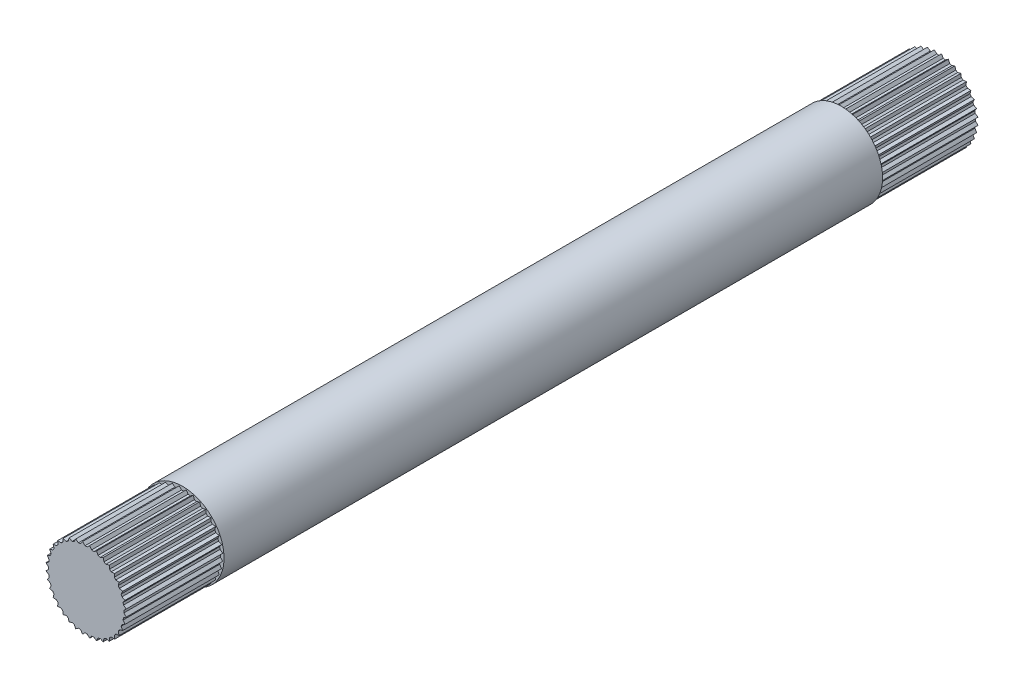
SolidWorks part; units mm, degrees
material "AISI 1015 Steel, Cold Drawn (SS)"
ref_plane "X-Y Datum" through (0, 0, 0) normal (0, 0, 1) x (1, 0, 0)
ref_plane "X-Z Datum" through (0, 0, 0) normal (0, 1, 0) x (1, 0, 0)
ref_plane "Y-Z Datum" through (0, 0, 0) normal (1, 0, 0) x (0, 0, -1)
sketch "Sketch9" plane through (0, 0, 0) normal (0, 1, 0) x (1, 0, 0)
  line L0 (16.002, 0) -> (0, 0)
  line L1 (0, 0) -> (0, -239.8166)
  line L2 (0, -239.8166) -> (-72.2493, -375.6979)
  dimension "D1" = 153.895
  dimension "D2" = 28
  dimension "D3" = 239.8166
  dimension "D5" = 16.002
sketch "Sketch5" plane through (0, 0, 0) normal (0, 1, 0) x (1, 0, 0)
  line L0 (7.9375, -218.2266) -> (7.9375, -22.1615)
  line L1 (7.9375, -22.1615) -> (9.525, -22.1615)
  line L2 (9.525, -22.1615) -> (9.525, -218.2266)
  line L3 (9.525, -218.2266) -> (7.9375, -218.2266)
  line L5 (16.002, 0) -> (0, 0) construction
  line L6 (0, 0) -> (0, -239.8166) construction
  line L7 (0, -239.8166) -> (9.525, -239.8166) construction
  line L8 (12.5602, -220.5666) -> (0, -220.5666) construction
  dimension "D1" = 1.5875
  dimension "D2" = 22.1615
  dimension "D3" = 7.9375
  dimension "D4" = 19.25
  dimension "D5" = 21.59
revolve "Revolve2" add sketch "Sketch5" angle 360 about L1
sketch "Sketch6" plane through (0, 0, 0) normal (0, 1, 0) x (1, 0, 0)
  circle A0 centre (0, -33.1635) radius 1.5875 construction
  circle A1 centre (0, -33.1635) radius 1.5875
sketch "Sketch7" plane through (0, 0, 0) normal (1, 0, 0) x (0, 0, -1)
  circle A2 centre (-39.196, 0) radius 1.5875
  circle A4 centre (-39.196, 0) radius 1.5875 construction
extrude "Cut-Extrude5" [suppressed] cut sketch "Sketch7" against normal through all both and the other way through all
extrude "Cut-Extrude6" [suppressed] cut sketch "Sketch6" against normal through all both and the other way through all
sketch "Sketch8" plane through (0, 0, 0) normal (0, 0, 1) x (1, 0, 0)
  line L0 (9.2357, -0.808) -> (8.6817, -0.254)
  line L1 (8.6817, -0.254) -> (8.6817, 0.254)
  line L2 (8.6817, 0.254) -> (9.2357, 0.808)
  line L3 (8.6817, 0) -> (0, 0) construction
  line L4 (8.9551, -2.3995) -> (8.5057, -1.7577)
  line L5 (8.5057, -1.7577) -> (8.5939, -1.2574)
  line L6 (8.5939, -1.2574) -> (9.2357, -0.808)
  line L7 (8.4024, -3.9181) -> (8.0713, -3.208)
  line L8 (8.0713, -3.208) -> (8.245, -2.7306)
  line L9 (8.245, -2.7306) -> (8.9551, -2.3995)
  line L10 (7.5944, -5.3176) -> (7.3916, -4.5608)
  line L11 (7.3916, -4.5608) -> (7.6456, -4.1209)
  line L12 (7.6456, -4.1209) -> (8.4024, -3.9181)
  line L13 (6.5556, -6.5556) -> (6.4873, -5.7751)
  line L14 (6.4873, -5.7751) -> (6.8138, -5.3859)
  line L15 (6.8138, -5.3859) -> (7.5944, -5.3176)
  line L16 (5.3176, -7.5944) -> (5.3859, -6.8138)
  line L17 (5.3859, -6.8138) -> (5.7751, -6.4873)
  line L18 (5.7751, -6.4873) -> (6.5556, -6.5556)
  line L19 (3.9181, -8.4024) -> (4.1209, -7.6456)
  line L20 (4.1209, -7.6456) -> (4.5608, -7.3916)
  line L21 (4.5608, -7.3916) -> (5.3176, -7.5944)
  line L22 (2.3995, -8.9551) -> (2.7306, -8.245)
  line L23 (2.7306, -8.245) -> (3.208, -8.0713)
  line L24 (3.208, -8.0713) -> (3.9181, -8.4024)
  line L25 (0.808, -9.2357) -> (1.2574, -8.5939)
  line L26 (1.2574, -8.5939) -> (1.7577, -8.5057)
  line L27 (1.7577, -8.5057) -> (2.3995, -8.9551)
  line L28 (-0.808, -9.2357) -> (-0.254, -8.6817)
  line L29 (-0.254, -8.6817) -> (0.254, -8.6817)
  line L30 (0.254, -8.6817) -> (0.808, -9.2357)
  line L31 (-2.3995, -8.9551) -> (-1.7577, -8.5057)
  line L32 (-1.7577, -8.5057) -> (-1.2574, -8.5939)
  line L33 (-1.2574, -8.5939) -> (-0.808, -9.2357)
  line L34 (-3.9181, -8.4024) -> (-3.208, -8.0713)
  line L35 (-3.208, -8.0713) -> (-2.7306, -8.245)
  line L36 (-2.7306, -8.245) -> (-2.3995, -8.9551)
  line L37 (-5.3176, -7.5944) -> (-4.5608, -7.3916)
  line L38 (-4.5608, -7.3916) -> (-4.1209, -7.6456)
  line L39 (-4.1209, -7.6456) -> (-3.9181, -8.4024)
  line L40 (-6.5556, -6.5556) -> (-5.7751, -6.4873)
  line L41 (-5.7751, -6.4873) -> (-5.3859, -6.8138)
  line L42 (-5.3859, -6.8138) -> (-5.3176, -7.5944)
  line L43 (-7.5944, -5.3176) -> (-6.8138, -5.3859)
  line L44 (-6.8138, -5.3859) -> (-6.4873, -5.7751)
  line L45 (-6.4873, -5.7751) -> (-6.5556, -6.5556)
  line L46 (-8.4024, -3.9181) -> (-7.6456, -4.1209)
  line L47 (-7.6456, -4.1209) -> (-7.3916, -4.5608)
  line L48 (-7.3916, -4.5608) -> (-7.5944, -5.3176)
  line L49 (-8.9551, -2.3995) -> (-8.245, -2.7306)
  line L50 (-8.245, -2.7306) -> (-8.0713, -3.208)
  line L51 (-8.0713, -3.208) -> (-8.4024, -3.9181)
  line L52 (-9.2357, -0.808) -> (-8.5939, -1.2574)
  line L53 (-8.5939, -1.2574) -> (-8.5057, -1.7577)
  line L54 (-8.5057, -1.7577) -> (-8.9551, -2.3995)
  line L55 (-9.2357, 0.808) -> (-8.6817, 0.254)
  line L56 (-8.6817, 0.254) -> (-8.6817, -0.254)
  line L57 (-8.6817, -0.254) -> (-9.2357, -0.808)
  line L58 (-8.9551, 2.3995) -> (-8.5057, 1.7577)
  line L59 (-8.5057, 1.7577) -> (-8.5939, 1.2574)
  line L60 (-8.5939, 1.2574) -> (-9.2357, 0.808)
  line L61 (-8.4024, 3.9181) -> (-8.0713, 3.208)
  line L62 (-8.0713, 3.208) -> (-8.245, 2.7306)
  line L63 (-8.245, 2.7306) -> (-8.9551, 2.3995)
  line L64 (-7.5944, 5.3176) -> (-7.3916, 4.5608)
  line L65 (-7.3916, 4.5608) -> (-7.6456, 4.1209)
  line L66 (-7.6456, 4.1209) -> (-8.4024, 3.9181)
  line L67 (-6.5556, 6.5556) -> (-6.4873, 5.7751)
  line L68 (-6.4873, 5.7751) -> (-6.8138, 5.3859)
  line L69 (-6.8138, 5.3859) -> (-7.5944, 5.3176)
  line L70 (-5.3176, 7.5944) -> (-5.3859, 6.8138)
  line L71 (-5.3859, 6.8138) -> (-5.7751, 6.4873)
  line L72 (-5.7751, 6.4873) -> (-6.5556, 6.5556)
  line L73 (-3.9181, 8.4024) -> (-4.1209, 7.6456)
  line L74 (-4.1209, 7.6456) -> (-4.5608, 7.3916)
  line L75 (-4.5608, 7.3916) -> (-5.3176, 7.5944)
  line L76 (-2.3995, 8.9551) -> (-2.7306, 8.245)
  line L77 (-2.7306, 8.245) -> (-3.208, 8.0713)
  line L78 (-3.208, 8.0713) -> (-3.9181, 8.4024)
  line L79 (-0.808, 9.2357) -> (-1.2574, 8.5939)
  line L80 (-1.2574, 8.5939) -> (-1.7577, 8.5057)
  line L81 (-1.7577, 8.5057) -> (-2.3995, 8.9551)
  line L82 (0.808, 9.2357) -> (0.254, 8.6817)
  line L83 (0.254, 8.6817) -> (-0.254, 8.6817)
  line L84 (-0.254, 8.6817) -> (-0.808, 9.2357)
  line L85 (2.3995, 8.9551) -> (1.7577, 8.5057)
  line L86 (1.7577, 8.5057) -> (1.2574, 8.5939)
  line L87 (1.2574, 8.5939) -> (0.808, 9.2357)
  line L88 (3.9181, 8.4024) -> (3.208, 8.0713)
  line L89 (3.208, 8.0713) -> (2.7306, 8.245)
  line L90 (2.7306, 8.245) -> (2.3995, 8.9551)
  line L91 (5.3176, 7.5944) -> (4.5608, 7.3916)
  line L92 (4.5608, 7.3916) -> (4.1209, 7.6456)
  line L93 (4.1209, 7.6456) -> (3.9181, 8.4024)
  line L94 (6.5556, 6.5556) -> (5.7751, 6.4873)
  line L95 (5.7751, 6.4873) -> (5.3859, 6.8138)
  line L96 (5.3859, 6.8138) -> (5.3176, 7.5944)
  line L97 (7.5944, 5.3176) -> (6.8138, 5.3859)
  line L98 (6.8138, 5.3859) -> (6.4873, 5.7751)
  line L99 (6.4873, 5.7751) -> (6.5556, 6.5556)
  line L100 (8.4024, 3.9181) -> (7.6456, 4.1209)
  line L101 (7.6456, 4.1209) -> (7.3916, 4.5608)
  line L102 (7.3916, 4.5608) -> (7.5944, 5.3176)
  line L103 (8.9551, 2.3995) -> (8.245, 2.7306)
  line L104 (8.245, 2.7306) -> (8.0713, 3.208)
  line L105 (8.0713, 3.208) -> (8.4024, 3.9181)
  line L106 (9.2357, 0.808) -> (8.5939, 1.2574)
  line L107 (8.5939, 1.2574) -> (8.5057, 1.7577)
  line L108 (8.5057, 1.7577) -> (8.9551, 2.3995)
  circle A0 centre (0, 0) radius 12.7
  circle A1 centre (0, 0) radius 9.271 construction
  circle A2 centre (0, 0) radius 8.6854 construction
  point P153 (0, 0)
  dimension "D1" = 25.4
  dimension "D4" = 18.542
  dimension "D6" = 17.3708
  dimension "D2" = 0.508
  dimension "D3" = 135
  dimension "D5" = 36
extrude "Cut-Extrude7" cut sketch "Sketch8" against normal blind 22.225 from surface starting at face at (-9.525, 0, 218.2266)
ref_plane "Plane1" through (0, 0, 47.5615) normal (0, 0, -1) x (-1, 0, 0)
sketch "Sketch10" plane through (0, 0, 47.5615) normal (0, 0, -1) x (-1, 0, 0)
  circle A0 centre (0, 0) radius 7.9375
  dimension "D1" = 15.875
extrude "Boss-Extrude1" add sketch "Sketch10" against normal up to surface (170.6651 mm away) up to face at (-7.9375, 0, 218.2266)
sketch "Sketch11" plane through (0, 0, 22.1615) normal (0, 0, -1) x (-1, 0, 0)
  line L0 (0, 9.525) -> (13.3548, 9.525) construction
  line L1 (0, 9.525) -> (0, 15.4312) construction
  line L2 (-9.525, 0) -> (-9.525, 9.1744) construction
  line L3 (-9.525, 0) -> (-16.674, 0) construction
  circle A0 centre (0, 0) radius 9.525 construction
  point P0 (0, 9.525)
  point P1 (-9.525, 0)
extrude "Cut-Extrude8" cut sketch "Sketch8<2>" along normal blind 44.4119
sketch "Sketch8<2>" plane through (0, 0, 0) normal (0, 0, 1) x (1, 0, 0) same geometry as "Sketch8"
